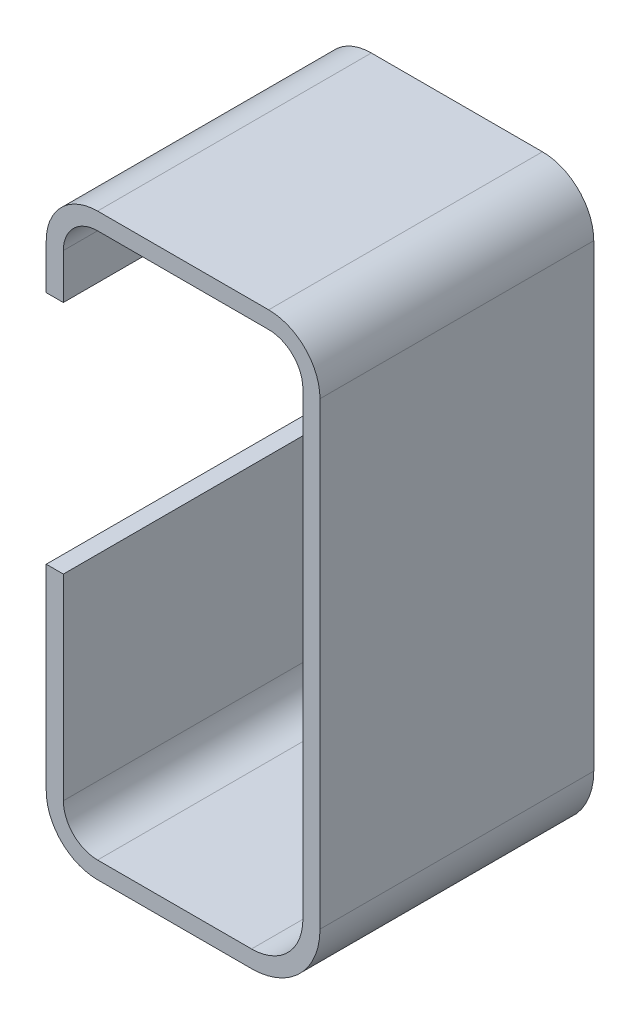
SolidWorks part; units mm, degrees
ref_plane "Front Plane" through (0, 0, 0) normal (0, 0, 1) x (1, 0, 0)
ref_plane "Top Plane" through (0, 0, 0) normal (0, 1, 0) x (1, 0, 0)
ref_plane "Right Plane" through (0, 0, 0) normal (1, 0, 0) x (0, 0, -1)
sketch "Sketch1" plane through (0, 0, 0) normal (0, 0, 1) x (1, 0, 0)
  line L0 (-23.0418, -271.5263) -> (-23.0418, -283)
  line L1 (-20.0418, -286) -> (-11.0418, -286)
  line L2 (-7.0418, -286) -> (-7.0418, 286) construction
  line L3 (-7.0418, -286) -> (-17.0418, -286) construction
  line L4 (-7.0418, -282) -> (-7.0418, -255.1509)
  line L5 (-10.0418, -252.1509) -> (-20.0418, -252.1509)
  line L6 (-23.0418, -255.1509) -> (-23.0418, -257.7831)
  line L7 (-12.0418, -285.4124) -> (-18.0418, -285.4124) construction
  line L8 (-12.0418, -295.0001) -> (-12.0418, -277.4138) construction
  line L9 (-18.0418, -277.1638) -> (-18.0418, -291.7831) construction
  line L10 (-15.0418, -285.4124) -> (-15.0418, -262.7805) construction
  line L11 (-22.0418, -271.5263) -> (-22.0418, -283)
  line L12 (-20.0418, -285) -> (-11.0418, -285)
  line L13 (-8.0418, -282) -> (-8.0418, -255.1509)
  line L14 (-10.0418, -253.1509) -> (-20.0418, -253.1509)
  line L15 (-22.0418, -255.1509) -> (-22.0418, -257.7831)
  line L16 (-22.0418, -257.7831) -> (-23.0418, -257.7831)
  line L17 (-23.0418, -271.5263) -> (-22.0418, -271.5263)
  arc A0 (-23.0418, -283) -> (-20.0418, -286) centre (-20.0418, -283) ccw
  arc A1 (-7.0418, -255.1509) -> (-10.0418, -252.1509) centre (-10.0418, -255.1509) ccw
  arc A2 (-20.0418, -252.1509) -> (-23.0418, -255.1509) centre (-20.0418, -255.1509) ccw
  arc A3 (-11.0418, -286) -> (-7.0418, -282) centre (-11.0418, -282) ccw
  arc A4 (-22.0418, -283) -> (-20.0418, -285) centre (-20.0418, -283) ccw
  arc A5 (-11.0418, -285) -> (-8.0418, -282) centre (-11.0418, -282) ccw
  arc A6 (-8.0418, -255.1509) -> (-10.0418, -253.1509) centre (-10.0418, -255.1509) ccw
  arc A7 (-20.0418, -253.1509) -> (-22.0418, -255.1509) centre (-20.0418, -255.1509) ccw
  point P14 (-7.0418, -252.1509)
  point P19 (-7.0418, -286)
  dimension "D1" = 3
  dimension "D2" = 4
  dimension "D3" = 16
  dimension "D4" = 8
  dimension "D5" = 1
extrude "Boss-Extrude1" add sketch "Sketch1" along normal blind 8 and the other way blind 8
